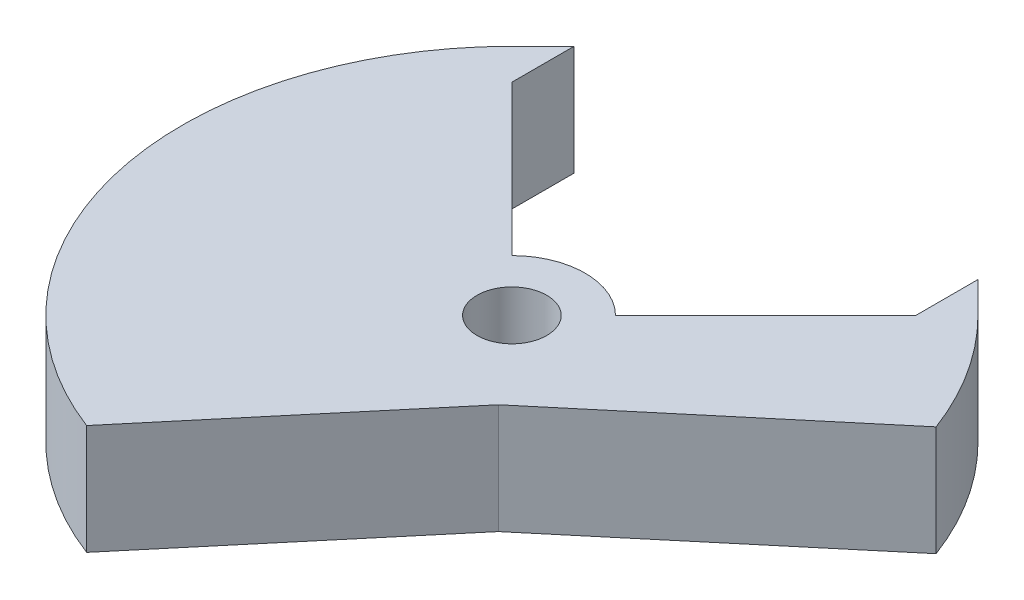
SolidWorks part; units mm, degrees
material "ABS"
ref_plane "Front Plane" through (0, 0, 0) normal (0, 0, 1) x (1, 0, 0)
ref_plane "Top Plane" through (0, 0, 0) normal (0, 1, 0) x (1, 0, 0)
ref_plane "Right Plane" through (0, 0, 0) normal (1, 0, 0) x (0, 0, -1)
sketch "Sketch1" plane through (0, 0, 0) normal (0, 1, 0) x (1, 0, 0)
  line L0 (-31.8198, 31.8198) -> (-7.0711, 7.0711)
  line L1 (7.0711, 7.0711) -> (31.8198, 31.8198)
  line L2 (0, 0) -> (0, 20) construction
  line L3 (0, 0) -> (-7.0711, 7.0711) construction
  line L4 (7.0711, 7.0711) -> (0, 0) construction
  arc A0 (-31.8198, 31.8198) -> (31.8198, 31.8198) centre (0, 0) ccw
  circle A1 centre (0, 0) radius 4.7625
  arc A2 (7.0711, 7.0711) -> (-7.0711, 7.0711) centre (0, 0) ccw
  dimension "D1" = 9.525
  dimension "D2" = 90
  dimension "D3" = 20
  dimension "D4" = 45
extrude "Boss-Extrude1" add sketch "Sketch1" along normal blind 15
sketch "Sketch2" plane through (0, 15, 0) normal (0, 1, 0) x (1, 0, 0)
  line L0 (4.0536, 2.5) -> (4.0536, -2.5)
  arc A0 (4.0536, -2.5) -> (4.0536, 2.5) centre (0, 0) ccw
  circle A1 centre (0, 0) radius 4.7625 construction
  dimension "D1" = 5
extrude "Shaft D" [suppressed] add sketch "Sketch2" against normal up to surface (10 mm away) up to face at (0, 0, -0.9727)
sketch "Sketch3" plane through (0, 15, 0) normal (0, 1, 0) x (1, 0, 0)
  line L0 (-31.8198, 31.8198) -> (-27.5772, 36.0624)
  line L1 (-27.5772, 36.0624) -> (-27.5772, 27.5772)
  line L2 (-7.0711, 7.0711) -> (-31.8198, 31.8198) construction
  line L3 (-27.5772, 27.5772) -> (-31.8198, 31.8198)
  line L4 (0, 0) -> (0, 30.6174) construction
  line L5 (27.5772, 27.5772) -> (31.8198, 31.8198)
  line L6 (27.5772, 36.0624) -> (27.5772, 27.5772)
  line L7 (31.8198, 31.8198) -> (27.5772, 36.0624)
  dimension "D1" = 6
extrude "Boss-Extrude2" add sketch "Sketch3" against normal up to surface (15 mm away) up to face at (0, 0, -0.9727)
sketch "Sketch4" plane through (0, 15, 0) normal (0, 1, 0) x (1, 0, 0)
  line L0 (-148.943, 0) -> (142.5774, 0) construction
  line L1 (0, 0) -> (-79.8469, -95.1578) construction
  line L2 (0, 0) -> (41.4751, -49.4281) construction
  line L8 (0, 0) -> (49.4281, 41.4751) construction
  line L9 (0, 0) -> (95.1578, -79.8469) construction
  line L10 (-79.8469, -95.1578) -> (95.1578, -79.8469) construction
  line L11 (49.4281, 41.4751) -> (41.4751, -49.4281) construction
  line L14 (9.6418, -11.4907) -> (50.1771, 22.5225)
  line L15 (9.6418, -11.4907) -> (-22.7382, -50.0797)
  arc A2 (-22.7382, -50.0797) -> (50.1771, 22.5225) centre (0, 0) ccw
  point P8 (-22.7495, -50.0745)
  dimension "D4" = 55
  dimension "D1" = 50
  dimension "D3" = 50
  dimension "D5" = 15
extrude "Cut-Extrude1" cut sketch "Sketch4" against normal through all
